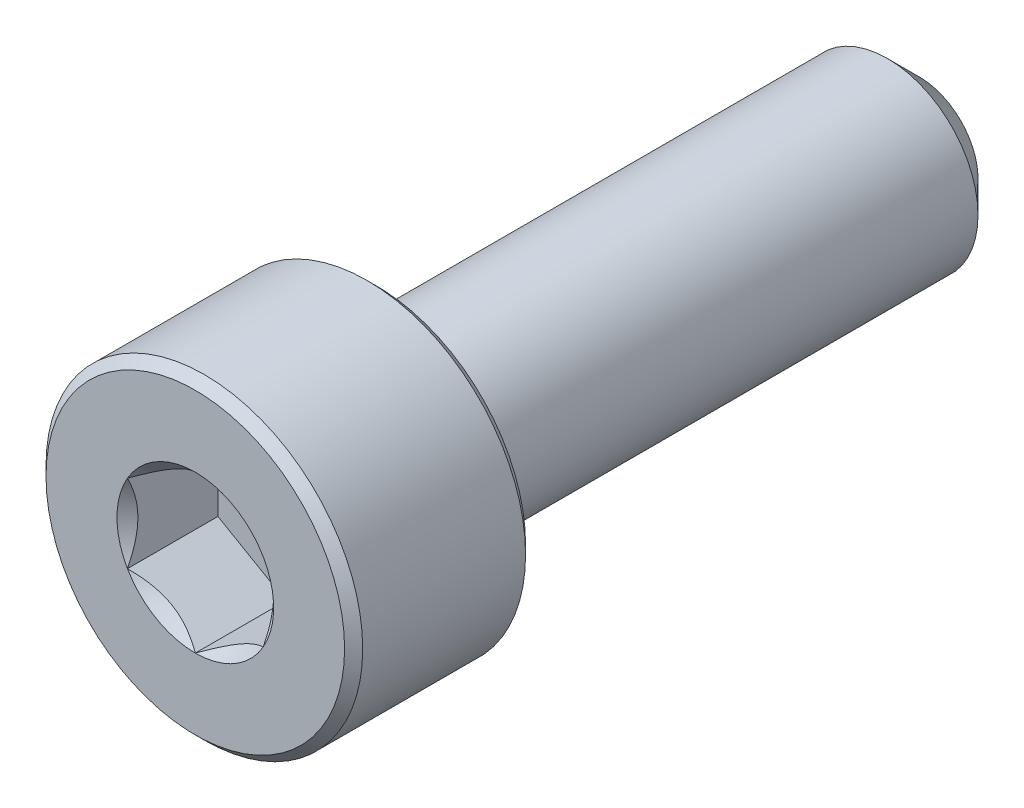
SolidWorks part; units mm, degrees
material "Alloy Steel"
ref_plane "Front Plane" through (0, 0, 0) normal (0, 0, 1) x (1, 0, 0)
ref_plane "Top Plane" through (0, 0, 0) normal (0, 1, 0) x (1, 0, 0)
ref_plane "Right Plane" through (0, 0, 0) normal (1, 0, 0) x (0, 0, -1)
sketch "Sketch1" plane through (0, 0, 0) normal (1, 0, 0) x (0, 0, -1)
  line L0 (-8, 0) -> (8, 0) construction
  line L1 (8, 0) -> (8, 1.3) construction
  line L2 (8, 1.3) -> (7.3, 2) construction
  line L3 (7.3, 2) -> (-4, 2) construction
  line L5 (-4, 2) -> (-4, 3.5) construction
  line L6 (-4, 3.5) -> (-8, 3.5) construction
  line L7 (-8, 3.5) -> (-8, 0) construction
  line L8 (8, 1.3) -> (8, 2) construction
  line L9 (7.9563, 2.0758) -> (8.3063, 1.4696) construction
  line L10 (8.3063, 1.4696) -> (8.6562, 2.0758) construction
  line L11 (8.6562, 2.0758) -> (7.9563, 2.0758) construction
  line L12 (8.3063, 2.0758) -> (8.3063, 2) construction
  line L13 (8.3063, 1.4696) -> (8.3063, 1.5453) construction
  line L14 (8.2625, 1.5453) -> (8.35, 1.5453) construction
  line L15 (8, 2) -> (8.6125, 2) construction
  line L16 (7.9781, 2.0379) -> (8.6344, 2.0379) construction
  line L17 (8, 0) -> (8, -2) construction
  line L18 (-4.2, 3.5) -> (-4, 3.3) construction
  line L19 (-7.8, 3.5) -> (-8, 3.3) construction
  point P0 (-8, 1.5)
  point P3 (5.55, 2)
  point P4 (0, 0)
  point P22 (8.3063, 1.5453)
  point P24 (-4, 2)
  point P25 (8.3063, 2)
  point P28 (8.3063, 2.0379)
  point P29 (5.55, -2)
  point P31 (-6, 3.5)
  point P37 (-4.7, 3.5)
  point P38 (-7.7, 3.5)
  point P41 (-6, 0)
  dimension "head height" = 4
  dimension "D1" = 45
  dimension "Head Diameter" = 7
  dimension "Thread Size" = 4
  dimension "drive size" = 3
  dimension "Thread Pitch" = 0.7
  dimension "D2" = 0.0875
  dimension "D3" = 0.7
  dimension "D4" = 2.45
  dimension "D7" = 0.2
  dimension "D8" = 0.2
  dimension "D9" = 0.2
  dimension "D10" = 0.1
  dimension "D11" = 0.5
  dimension "length" = 12
  dimension "Drive Depth" = 2
sketch "Sketch2" plane through (0, 0, 0) normal (1, 0, 0) x (0, 0, -1)
  line L1 (-7.8, 3.5) -> (-4.2, 3.5)
  line L4 (7.3, 2) -> (8, 1.3)
  line L5 (8, 1.3) -> (8, 0)
  line L6 (-4.2, 3.5) -> (-4, 3.3) construction
  line L7 (8, 0) -> (-8, 0)
  line L8 (-7.8, 3.5) -> (-8, 3.3) construction
  line L9 (-4.2, 3.5) -> (-4, 3.3)
  line L10 (-7.8, 3.5) -> (-8, 3.3)
  line L11 (-8, 3.3) -> (-8, 0)
  line L12 (-4, 3.3) -> (-4, 2)
  line L13 (-4, 2) -> (7.3, 2)
revolve "Revolve1" add sketch "Sketch2" angle 360 about L7
sketch "Sketch3" plane through (0, 0, 8) normal (0, 0, 1) x (1, 0, 0)
  line L1 (0, 1.7321) -> (-1.5, 0.866)
  line L2 (-1.5, 0.866) -> (-1.5, -0.866)
  line L3 (-1.5, -0.866) -> (0, -1.7321)
  line L4 (0, -1.7321) -> (1.5, -0.866)
  line L5 (1.5, -0.866) -> (1.5, 0.866)
  line L6 (1.5, 0.866) -> (0, 1.7321)
  circle A0 centre (0, 0) radius 1.5 construction
  dimension "D1" = 3
extrude "Cut-Extrude1" cut sketch "Sketch3" against normal up to vertex (2 mm away) up to point (0, 0, 6)
sketch "Sketch4" plane through (0, 0, 8) normal (0, 0, 1) x (1, 0, 0)
  circle A0 centre (0, 0) radius 1.7321
extrude "Cut-Extrude2" cut sketch "Sketch4" against normal blind 0.5 draft 45
ref_plane "Plane1" [suppressed] through (0, 0, 4) normal (0, 0, 1) x (1, 0, 0)
split "Split1" [suppressed] bodies to split 106
sketch "Sketch6" [suppressed] plane through (0, 0, -8) normal (0, 0, -1) x (-1, 0, 0)
  circle A0 centre (0, 0) radius 2
curve "Helix/Spiral1" [suppressed] pitch 0.7 height 12.7 turns 18.1429
sketch "Sketch7" [suppressed] plane through (0, 0, 0) normal (1, 0, 0) x (0, 0, -1)
  line L0 (7.9781, 2.0379) -> (8.6344, 2.0379)
  line L1 (8.6344, 2.0379) -> (8.35, 1.5453)
  line L2 (8.35, 1.5453) -> (8.2625, 1.5453)
  line L3 (8.2625, 1.5453) -> (7.9781, 2.0379)
sweep "Cut-Sweep1" [suppressed] cut profiles "Sketch7" path "Helix/Spiral1"
sketch "Sketch8" [suppressed] plane through (0, 0, 4) normal (0, 0, -1) x (-1, 0, 0)
  circle A0 centre (0, 0) radius 2
extrude "Boss-Extrude1" [suppressed] add sketch "Sketch8" along normal through all draft 45
ref_plane "Plane2" [suppressed] through (0, 0, 6) normal (0, 0, 1) x (1, 0, 0)
sketch "Sketch9" [suppressed] plane through (0, 0, 6) normal (0, 0, 1) x (1, 0, 0)
  line L0 (0, 3.4038) -> (0.0916, 3.4988)
  line L1 (0, 3.4038) -> (-0.0916, 3.4988)
  line L2 (0, 3.5) -> (0, 0) construction
  line L3 (-0.0916, 3.4988) -> (0, 0) construction
  line L4 (0, 0) -> (0.0916, 3.4988) construction
  arc A0 (0.0916, 3.4988) -> (-0.0916, 3.4988) centre (0, 0) ccw
  circle A1 centre (0, 0) radius 3.4038 construction
  dimension "D1" = 7
  dimension "D2" = 6.8075
  dimension "D3" = 3
extrude "Cut-Extrude4" [suppressed] cut sketch "Sketch9" against normal up to vertex and the other way up to vertex up to point (0, 3.5, 4.7) other way up to point (0, 3.5, 7.7)
pattern_circular "CirPattern2" [suppressed] count 96 over 360 about axis through (0, 0, 8) along (0, 0, -1) of bodies 113
equation "\"D2@Sketch1\" = \"Thread Pitch@Sketch1\" / 8"
equation "\"D3@Sketch1\" = \"Thread Pitch@Sketch1\""
equation "\"D3@Helix/Spiral1\" = \"length@Sketch1\" + \"Thread Pitch@Sketch1\""
equation "\"D4@Helix/Spiral1\" = \"Thread Pitch@Sketch1\""
equation "\"D4@Sketch1\" = \"Thread Pitch@Sketch1\" * 3.5"
equation "\"D7@Sketch1\"=\"head height@Sketch1\"*.05"
equation "\"D8@Sketch1\"=\"D7@Sketch1\""
equation "\"D9@Sketch1\"=\"D7@Sketch1\""
equation "\"D10@Sketch1\"=\"D7@Sketch1\"/2"
equation "\"D11@Sketch1\"=\"D10@Sketch1\"*5"
equation "\"D1@CirPattern2\"=( 360 / \"D3@Sketch9\" )*0.8"
equation "\"D1@Sketch3\" = \"drive size@Sketch1\""
equation "\"D2@Sketch9\"=\"Head Diameter@Sketch1\" * 0.9725"
